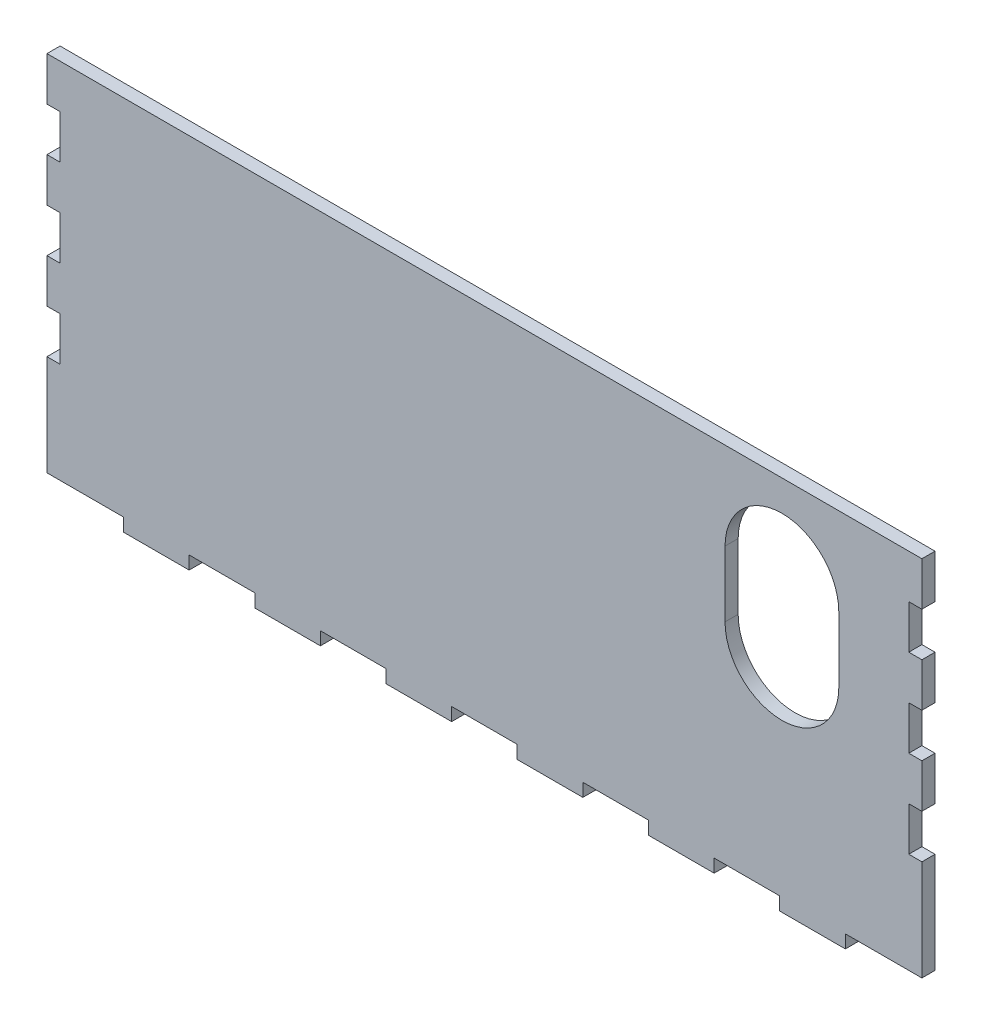
SolidWorks part; units mm, degrees
ref_plane "Front Plane" through (0, 0, 0) normal (0, 0, 1) x (1, 0, 0)
ref_plane "Top Plane" through (0, 0, 0) normal (0, 1, 0) x (1, 0, 0)
ref_plane "Right Plane" through (0, 0, 0) normal (1, 0, 0) x (0, 0, -1)
sketch "Sketch1" plane through (0, 0, 0) normal (0, 0, 1) x (1, 0, 0)
  line L0 (-97, 0) -> (97, 0) construction
  line L1 (0, -25.5) -> (0, 57.5) construction
  line L2 (100, -2.5) -> (97, -2.5)
  line L3 (-97, 57.5) -> (97, 57.5)
  line L4 (100, -25.5) -> (100, -2.5)
  line L5 (0, -25.5) -> (7.5, -25.5)
  line L6 (-97, -25.5) -> (-100, -25.5)
  line L7 (-100, -25.5) -> (-100, -2.5)
  line L8 (-97, 57.5) -> (-100, 57.5)
  line L9 (-100, 57.5) -> (-100, 47.5)
  line L10 (-100, 47.5) -> (-97, 47.5)
  line L11 (-97, 47.5) -> (-97, 37.5)
  line L12 (-97, 37.5) -> (-100, 37.5)
  line L13 (-100, 37.5) -> (-100, 27.5)
  line L14 (100, 17.5) -> (100, 7.5)
  line L15 (-100, 27.5) -> (-97, 27.5)
  line L16 (-97, 27.5) -> (-97, 17.5)
  line L17 (97, 7.5) -> (100, 7.5)
  line L18 (97, 17.5) -> (100, 17.5)
  line L19 (97, 7.5) -> (97, -2.5)
  line L20 (97, 27.5) -> (97, 17.5)
  line L21 (100, 27.5) -> (97, 27.5)
  line L22 (100, 37.5) -> (100, 27.5)
  line L23 (97, 37.5) -> (100, 37.5)
  line L24 (97, 47.5) -> (97, 37.5)
  line L25 (100, 47.5) -> (97, 47.5)
  line L26 (100, 57.5) -> (100, 47.5)
  line L27 (97, 57.5) -> (100, 57.5)
  line L28 (7.5, -25.5) -> (7.5, -28.5)
  line L29 (7.5, -28.5) -> (22.5, -28.5)
  line L30 (22.5, -28.5) -> (22.5, -25.5)
  line L31 (30, -25.5) -> (37.5, -25.5)
  line L32 (37.5, -25.5) -> (37.5, -28.5)
  line L33 (37.5, -28.5) -> (52.5, -28.5)
  line L34 (52.5, -28.5) -> (52.5, -25.5)
  line L35 (60, -25.5) -> (67.5, -25.5)
  line L36 (67.5, -25.5) -> (67.5, -28.5)
  line L37 (67.5, -28.5) -> (82.5, -28.5)
  line L38 (82.5, -28.5) -> (82.5, -25.5)
  line L39 (22.5, -25.5) -> (30, -25.5)
  line L40 (52.5, -25.5) -> (60, -25.5)
  line L41 (82.5, -25.5) -> (97, -25.5)
  line L42 (0, -25.5) -> (-7.5, -25.5)
  line L43 (-7.5, -25.5) -> (-7.5, -28.5)
  line L44 (-7.5, -28.5) -> (-22.5, -28.5)
  line L45 (-22.5, -28.5) -> (-22.5, -25.5)
  line L46 (-22.5, -25.5) -> (-37.5, -25.5)
  line L47 (-37.5, -25.5) -> (-37.5, -28.5)
  line L48 (-37.5, -28.5) -> (-52.5, -28.5)
  line L49 (-52.5, -28.5) -> (-52.5, -25.5)
  line L50 (-52.5, -25.5) -> (-67.5, -25.5)
  line L51 (-67.5, -25.5) -> (-67.5, -28.5)
  line L52 (-100, -2.5) -> (-97, -2.5)
  line L53 (97, -25.5) -> (100, -25.5)
  line L56 (-97, 7.5) -> (-97, -2.5)
  line L57 (-97, 17.5) -> (-100, 17.5)
  line L58 (-97, 7.5) -> (-100, 7.5)
  line L59 (-100, 17.5) -> (-100, 7.5)
  line L60 (-67.5, -28.5) -> (-82.5, -28.5)
  line L62 (-82.5, -28.5) -> (-82.5, -25.5)
  line L63 (-82.5, -25.5) -> (-97, -25.5)
  dimension "D2" = 7.5
  dimension "D4" = 83
  dimension "D5" = 10
  dimension "D6" = 194
  dimension "D8" = 7.5
  dimension "D9" = 15
  dimension "D10" = 3
  dimension "D11" = 10
  dimension "D7" = 10
  dimension "D13" = 10
  dimension "D12" = 10
  dimension "D14" = 7.5
  dimension "D15" = 14.5
  dimension "D16" = 10
  dimension "D18" = 3
  dimension "D19" = 15
  dimension "D20" = 15
  dimension "D21" = 15
  dimension "D22" = 15
  dimension "D23" = 15
extrude "Boss-Extrude1" add sketch "Sketch1" along normal blind 3
sketch "Sketch2" plane through (0, 0, 3) normal (0, 0, 1) x (1, 0, 0)
  line L0 (0, -25.5) -> (0, 22.5) construction
  line L1 (-7.5, -25.5) -> (7.5, -25.5) construction
  line L2 (0, 22.5) -> (68, 22.5) construction
  line L3 (68, 22.5) -> (68, 37.5) construction
  line L4 (55, 22.5) -> (55, 37.5)
  line L5 (81, 22.5) -> (81, 37.5)
  arc A0 (55, 22.5) -> (81, 22.5) centre (68, 22.5) ccw
  arc A1 (81, 37.5) -> (55, 37.5) centre (68, 37.5) ccw
  point P7 (68, 30)
  dimension "D4" = 13
  dimension "D1" = 48
  dimension "D2" = 68
  dimension "D3" = 15
extrude "Cut-Extrude1" cut sketch "Sketch2" against normal blind 10
